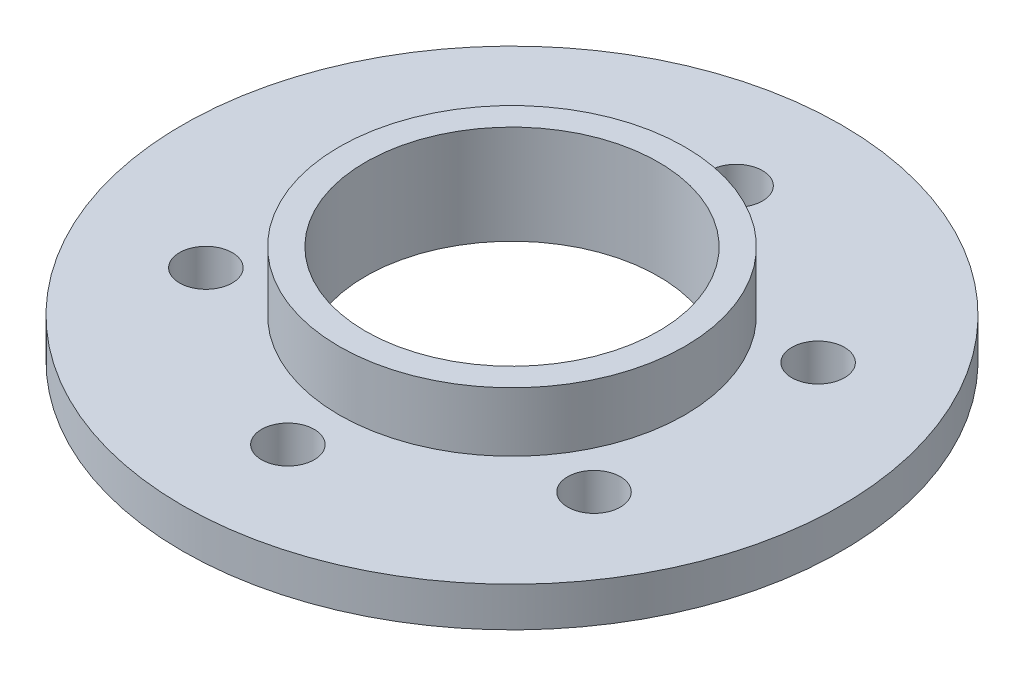
SolidWorks part; units mm, degrees
material "Aleación 6061"
ref_plane "Alzado" through (0, 0, 0) normal (0, 0, 1) x (1, 0, 0)
ref_plane "Planta" through (0, 0, 0) normal (0, 1, 0) x (1, 0, 0)
ref_plane "Vista lateral" through (0, 0, 0) normal (1, 0, 0) x (0, 0, -1)
sketch "Croquis1" plane through (0, 0, 0) normal (0, 1, 0) x (1, 0, 0)
  circle A0 centre (0, 0) radius 25
  circle A1 centre (0, 0) radius 4.7625
  dimension "D1" = 50
  dimension "D2" = 9.525
extrude "Saliente-Extruir1" add sketch "Croquis1" along normal blind 3
sketch "Croquis2" plane through (0, 3, 0) normal (0, 1, 0) x (1, 0, 0)
  line L0 (-17, 0) -> (17, 0) construction
  line L1 (0, -17) -> (0, 17) construction
  line L2 (-12.0208, 12.0208) -> (12.0208, -12.0208) construction
  line L3 (-12.0208, -12.0208) -> (12.0208, 12.0208) construction
  circle A0 centre (0, 0) radius 17 construction
  circle A1 centre (17, 0) radius 2 construction
  circle A2 centre (12.0208, 12.0208) radius 2 construction
  circle A3 centre (0, 17) radius 2
  circle A4 centre (-12.0208, 12.0208) radius 2 construction
  circle A5 centre (-17, 0) radius 2 construction
  circle A6 centre (-12.0208, -12.0208) radius 2 construction
  circle A7 centre (0, -17) radius 2 construction
  circle A8 centre (12.0208, -12.0208) radius 2 construction
  circle A9 centre (14.7224, 8.5) radius 2
  circle A10 centre (14.7224, -8.5) radius 2
  circle A11 centre (0, -17) radius 2
  circle A12 centre (-14.7224, -8.5) radius 2
  circle A13 centre (-14.7224, 8.5) radius 2
  point P19 (0, 0)
  point P31 (0, 0)
  dimension "D2" = 4
  dimension "D3" = 34
  dimension "D1" = 45
  dimension "D4" = 6
extrude "Cortar-Extruir1" cut sketch "Croquis2" against normal through all
sketch "Croquis3" plane through (0, 3, 0) normal (0, 1, 0) x (1, 0, 0)
  circle A0 centre (0, 0) radius 11.1125
  circle A1 centre (0, 0) radius 13.1125
  circle M12 centre (0, 0) radius 4.7625
  dimension "D1" = 22.225
  dimension "D2" = 2
extrude "Saliente-Extruir2" add sketch "Croquis3" along normal blind 4.5
extrude "Cortar-Extruir2" cut sketch "Croquis3<2>" against normal through all contours A0 M12 region at (-10.7982, 3, 0)
sketch "Croquis3<2>" plane through (0, 3, 0) normal (0, 1, 0) x (1, 0, 0) same geometry as "Croquis3"
